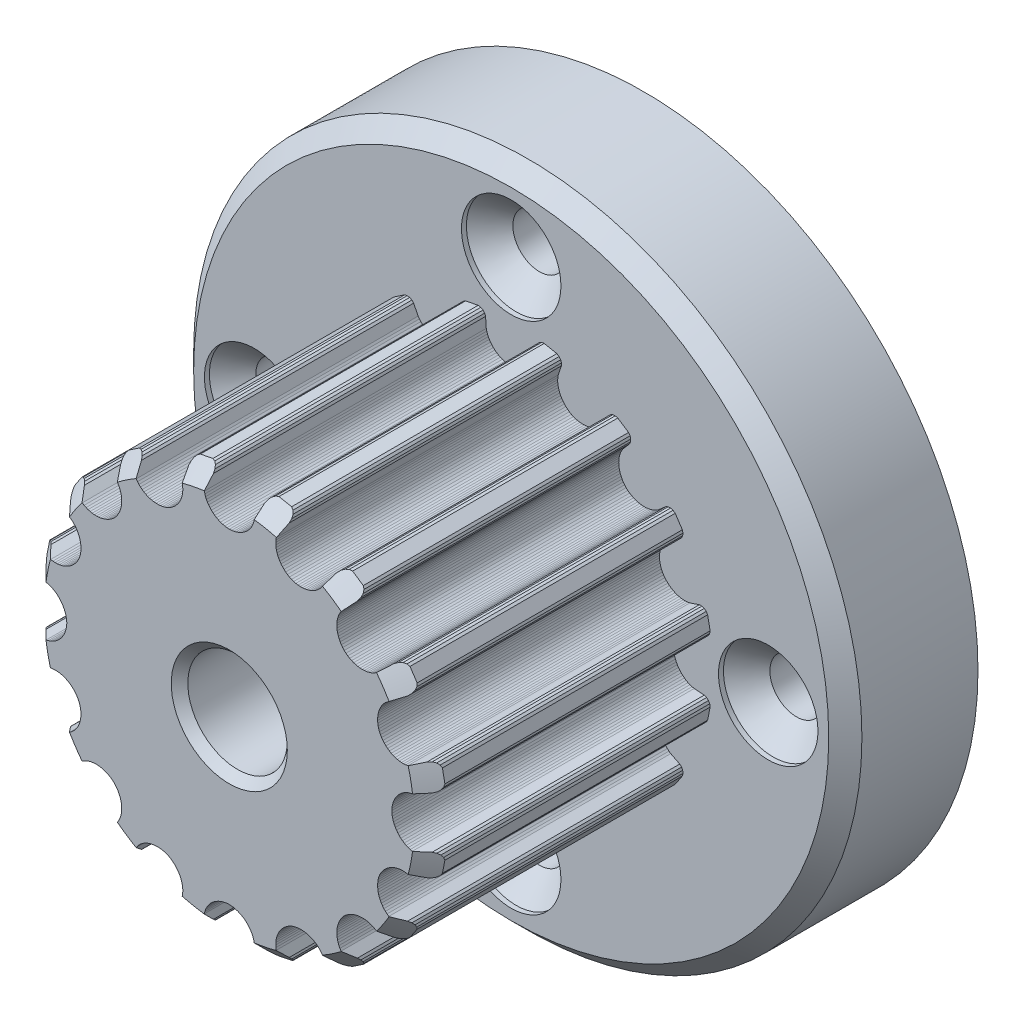
SolidWorks part; units mm, degrees
ref_plane "Front Plane" through (0, 0, 0) normal (0, 0, 1) x (1, 0, 0)
ref_plane "Top Plane" through (0, 0, 0) normal (0, 1, 0) x (1, 0, 0)
ref_plane "Right Plane" through (0, 0, 0) normal (1, 0, 0) x (0, 0, -1)
sketch "Sketch1" plane through (0, 0, 0) normal (0, 0, 1) x (1, 0, 0)
  circle A0 centre (0, 0) radius 15.5
  circle A1 centre (0, 15.5) radius 1.6
  circle A2 centre (15.5, 0) radius 1.6
  circle A3 centre (0, -15.5) radius 1.6
  circle A4 centre (-15.5, 0) radius 1.6
  circle A5 centre (0, 0) radius 20.15
  dimension "D1" = 31
  dimension "D2" = 3.2
  dimension "D3" = 40.3
extrude "Boss-Extrude1" add sketch "Sketch1" along normal blind 8 contours A5 A4 A0 A1 A2 A3 | A4 A0 A3 A2 A1 region at (0, 0, 0) region at (-19.5801, 0, 0)
sketch "Sketch8" plane through (0, 0, 8) normal (0, 0, 1) x (1, 0, 0)
  line L0 (-1.9904, -11.9969) -> (-1.8333, -11.9702)
  line L1 (-1.8333, -11.9702) -> (-1.6992, -11.8961)
  line L2 (-1.6992, -11.8961) -> (-1.5993, -11.7835)
  line L3 (-1.5993, -11.7835) -> (-1.5446, -11.6413)
  line L4 (-1.5446, -11.6413) -> (-1.5027, -11.0359)
  line L5 (-1.5027, -11.0359) -> (-1.4725, -10.9073)
  line L6 (-1.4725, -10.9073) -> (-1.4313, -10.7834)
  line L7 (-1.4313, -10.7834) -> (-1.3796, -10.6646)
  line L8 (-1.3796, -10.6646) -> (-1.3179, -10.5514)
  line L9 (-1.3179, -10.5514) -> (-1.2467, -10.4444)
  line L10 (-1.2467, -10.4444) -> (-1.1667, -10.3438)
  line L11 (-1.1667, -10.3438) -> (-1.0783, -10.2503)
  line L12 (-1.0783, -10.2503) -> (-0.9822, -10.1642)
  line L13 (-0.9822, -10.1642) -> (-0.8789, -10.086)
  line L14 (-0.8789, -10.086) -> (-0.7689, -10.0162)
  line L15 (-0.7689, -10.0162) -> (-0.6528, -9.9552)
  line L16 (-0.6528, -9.9552) -> (-0.5312, -9.9034)
  line L17 (-0.5312, -9.9034) -> (-0.4045, -9.8614)
  line L18 (-0.4045, -9.8614) -> (-0.2734, -9.8296)
  line L19 (-0.2734, -9.8296) -> (-0.1385, -9.8084)
  line L20 (-0.1385, -9.8084) -> (-0.0002, -9.7984)
  line L21 (-0.0002, -9.7984) -> (0.1382, -9.8084)
  line L22 (0.1382, -9.8084) -> (0.2733, -9.8295)
  line L23 (0.2733, -9.8295) -> (0.4045, -9.8613)
  line L24 (0.4045, -9.8613) -> (0.5312, -9.9032)
  line L25 (0.5312, -9.9032) -> (0.6529, -9.9549)
  line L26 (0.6529, -9.9549) -> (0.7691, -10.0159)
  line L27 (0.7691, -10.0159) -> (0.8791, -10.0858)
  line L28 (0.8791, -10.0858) -> (0.9825, -10.1639)
  line L29 (0.9825, -10.1639) -> (1.0786, -10.25)
  line L30 (1.0786, -10.25) -> (1.1669, -10.3436)
  line L31 (1.1669, -10.3436) -> (1.247, -10.4442)
  line L32 (1.247, -10.4442) -> (1.3181, -10.5512)
  line L33 (1.3181, -10.5512) -> (1.3798, -10.6644)
  line L34 (1.3798, -10.6644) -> (1.4315, -10.7832)
  line L35 (1.4315, -10.7832) -> (1.4726, -10.9072)
  line L36 (1.4726, -10.9072) -> (1.5027, -11.0359)
  line L37 (1.5027, -11.0359) -> (1.5446, -11.6413)
  line L38 (1.5446, -11.6413) -> (1.5993, -11.7835)
  line L39 (1.5993, -11.7835) -> (1.6992, -11.8961)
  line L40 (1.6992, -11.8961) -> (1.8333, -11.9702)
  line L41 (1.8333, -11.9702) -> (1.9904, -11.9969)
  line L42 (1.9904, -11.9969) -> (2.7522, -11.8454)
  line L43 (2.7522, -11.8454) -> (2.8871, -11.7606)
  line L44 (2.8871, -11.7606) -> (2.9825, -11.6408)
  line L45 (2.9825, -11.6408) -> (3.0317, -11.4985)
  line L46 (3.0317, -11.4985) -> (3.0279, -11.3462)
  line L47 (3.0279, -11.3462) -> (2.835, -10.7709)
  line L48 (2.835, -10.7709) -> (2.8136, -10.6405)
  line L49 (2.8136, -10.6405) -> (2.8042, -10.5103)
  line L50 (2.8042, -10.5103) -> (2.8066, -10.3807)
  line L51 (2.8066, -10.3807) -> (2.8203, -10.2526)
  line L52 (2.8203, -10.2526) -> (2.8451, -10.1264)
  line L53 (2.8451, -10.1264) -> (2.8805, -10.0029)
  line L54 (2.8805, -10.0029) -> (2.9264, -9.8827)
  line L55 (2.9264, -9.8827) -> (2.9822, -9.7664)
  line L56 (2.9822, -9.7664) -> (3.0478, -9.6546)
  line L57 (3.0478, -9.6546) -> (3.1227, -9.548)
  line L58 (3.1227, -9.548) -> (3.2066, -9.4472)
  line L59 (3.2066, -9.4472) -> (3.2992, -9.3528)
  line L60 (3.2992, -9.3528) -> (3.4001, -9.2656)
  line L61 (3.4001, -9.2656) -> (3.509, -9.186)
  line L62 (3.509, -9.186) -> (3.6256, -9.1148)
  line L63 (3.6256, -9.1148) -> (3.7495, -9.0526)
  line L64 (3.7495, -9.0526) -> (3.8812, -9.0089)
  line L65 (3.8812, -9.0089) -> (4.0141, -8.9767)
  line L66 (4.0141, -8.9767) -> (4.1474, -8.9558)
  line L67 (4.1474, -8.9558) -> (4.2806, -8.9461)
  line L68 (4.2806, -8.9461) -> (4.4128, -8.9473)
  line L69 (4.4128, -8.9473) -> (4.5435, -8.9592)
  line L70 (4.5435, -8.9592) -> (4.6718, -8.9816)
  line L71 (4.6718, -8.9816) -> (4.7972, -9.0143)
  line L72 (4.7972, -9.0143) -> (4.919, -9.057)
  line L73 (4.919, -9.057) -> (5.0364, -9.1097)
  line L74 (5.0364, -9.1097) -> (5.1488, -9.1719)
  line L75 (5.1488, -9.1719) -> (5.2555, -9.2437)
  line L76 (5.2555, -9.2437) -> (5.3558, -9.3246)
  line L77 (5.3558, -9.3246) -> (5.4491, -9.4146)
  line L78 (5.4491, -9.4146) -> (5.5345, -9.5134)
  line L79 (5.5345, -9.5134) -> (5.6115, -9.6208)
  line L80 (5.6115, -9.6208) -> (5.882, -10.164)
  line L81 (5.882, -10.164) -> (5.9869, -10.2745)
  line L82 (5.9869, -10.2745) -> (6.1223, -10.3403)
  line L83 (6.1223, -10.3403) -> (6.2745, -10.3575)
  line L84 (6.2745, -10.3575) -> (6.4299, -10.322)
  line L85 (6.4299, -10.322) -> (7.0757, -9.8905)
  line L86 (7.0757, -9.8905) -> (7.1679, -9.7605)
  line L87 (7.1679, -9.7605) -> (7.2103, -9.6133)
  line L88 (7.2103, -9.6133) -> (7.2013, -9.4631)
  line L89 (7.2013, -9.4631) -> (7.1394, -9.3238)
  line L90 (7.1394, -9.3238) -> (6.741, -8.8661)
  line L91 (6.741, -8.8661) -> (6.6714, -8.7539)
  line L92 (6.6714, -8.7539) -> (6.6129, -8.6371)
  line L93 (6.6129, -8.6371) -> (6.5655, -8.5165)
  line L94 (6.5655, -8.5165) -> (6.5291, -8.3929)
  line L95 (6.5291, -8.3929) -> (6.5037, -8.2669)
  line L96 (6.5037, -8.2669) -> (6.4892, -8.1392)
  line L97 (6.4892, -8.1392) -> (6.4856, -8.0106)
  line L98 (6.4856, -8.0106) -> (6.4926, -7.8817)
  line L99 (6.4926, -7.8817) -> (6.5104, -7.7534)
  line L100 (6.5104, -7.7534) -> (6.5388, -7.6262)
  line L101 (6.5388, -7.6262) -> (6.5778, -7.501)
  line L102 (6.5778, -7.501) -> (6.6272, -7.3784)
  line L103 (6.6272, -7.3784) -> (6.687, -7.2591)
  line L104 (6.687, -7.2591) -> (6.7572, -7.1439)
  line L105 (6.7572, -7.1439) -> (6.8377, -7.0335)
  line L106 (6.8377, -7.0335) -> (6.9284, -6.9286)
  line L107 (6.9284, -6.9286) -> (7.0333, -6.8378)
  line L108 (7.0333, -6.8378) -> (7.1438, -6.7572)
  line L109 (7.1438, -6.7572) -> (7.259, -6.6869)
  line L110 (7.259, -6.6869) -> (7.3783, -6.627)
  line L111 (7.3783, -6.627) -> (7.5009, -6.5775)
  line L112 (7.5009, -6.5775) -> (7.6262, -6.5385)
  line L113 (7.6262, -6.5385) -> (7.7533, -6.5101)
  line L114 (7.7533, -6.5101) -> (7.8817, -6.4923)
  line L115 (7.8817, -6.4923) -> (8.0105, -6.4852)
  line L116 (8.0105, -6.4852) -> (8.1392, -6.4889)
  line L117 (8.1392, -6.4889) -> (8.2669, -6.5034)
  line L118 (8.2669, -6.5034) -> (8.3929, -6.5288)
  line L119 (8.3929, -6.5288) -> (8.5165, -6.5652)
  line L120 (8.5165, -6.5652) -> (8.6371, -6.6127)
  line L121 (8.6371, -6.6127) -> (8.7539, -6.6713)
  line L122 (8.7539, -6.6713) -> (8.8661, -6.741)
  line L123 (8.8661, -6.741) -> (9.3238, -7.1394)
  line L124 (9.3238, -7.1394) -> (9.4631, -7.2013)
  line L125 (9.4631, -7.2013) -> (9.6133, -7.2103)
  line L126 (9.6133, -7.2103) -> (9.7605, -7.1679)
  line L127 (9.7605, -7.1679) -> (9.8905, -7.0757)
  line L128 (9.8905, -7.0757) -> (10.322, -6.4299)
  line L129 (10.322, -6.4299) -> (10.3575, -6.2745)
  line L130 (10.3575, -6.2745) -> (10.3403, -6.1223)
  line L131 (10.3403, -6.1223) -> (10.2745, -5.9869)
  line L132 (10.2745, -5.9869) -> (10.164, -5.882)
  line L133 (10.164, -5.882) -> (9.6208, -5.6115)
  line L134 (9.6208, -5.6115) -> (9.5135, -5.5345)
  line L135 (9.5135, -5.5345) -> (9.4148, -5.449)
  line L136 (9.4148, -5.449) -> (9.3248, -5.3558)
  line L137 (9.3248, -5.3558) -> (9.2439, -5.2554)
  line L138 (9.2439, -5.2554) -> (9.1722, -5.1487)
  line L139 (9.1722, -5.1487) -> (9.11, -5.0363)
  line L140 (9.11, -5.0363) -> (9.0574, -4.9189)
  line L141 (9.0574, -4.9189) -> (9.0146, -4.7971)
  line L142 (9.0146, -4.7971) -> (8.9819, -4.6717)
  line L143 (8.9819, -4.6717) -> (8.9595, -4.5434)
  line L144 (8.9595, -4.5434) -> (8.9476, -4.4128)
  line L145 (8.9476, -4.4128) -> (8.9463, -4.2806)
  line L146 (8.9463, -4.2806) -> (8.956, -4.1475)
  line L147 (8.956, -4.1475) -> (8.9767, -4.0143)
  line L148 (8.9767, -4.0143) -> (9.0088, -3.8815)
  line L149 (9.0088, -3.8815) -> (9.0524, -3.7498)
  line L150 (9.0524, -3.7498) -> (9.1147, -3.6258)
  line L151 (9.1147, -3.6258) -> (9.1859, -3.5091)
  line L152 (9.1859, -3.5091) -> (9.2654, -3.4)
  line L153 (9.2654, -3.4) -> (9.3527, -3.299)
  line L154 (9.3527, -3.299) -> (9.447, -3.2064)
  line L155 (9.447, -3.2064) -> (9.5478, -3.1224)
  line L156 (9.5478, -3.1224) -> (9.6544, -3.0475)
  line L157 (9.6544, -3.0475) -> (9.7662, -2.9819)
  line L158 (9.7662, -2.9819) -> (9.8826, -2.926)
  line L159 (9.8826, -2.926) -> (10.0028, -2.8802)
  line L160 (10.0028, -2.8802) -> (10.1263, -2.8448)
  line L161 (10.1263, -2.8448) -> (10.2525, -2.82)
  line L162 (10.2525, -2.82) -> (10.3807, -2.8064)
  line L163 (10.3807, -2.8064) -> (10.5102, -2.8041)
  line L164 (10.5102, -2.8041) -> (10.6405, -2.8135)
  line L165 (10.6405, -2.8135) -> (10.7709, -2.835)
  line L166 (10.7709, -2.835) -> (11.3462, -3.0279)
  line L167 (11.3462, -3.0279) -> (11.4985, -3.0317)
  line L168 (11.4985, -3.0317) -> (11.6408, -2.9825)
  line L169 (11.6408, -2.9825) -> (11.7606, -2.8871)
  line L170 (11.7606, -2.8871) -> (11.8454, -2.7522)
  line L171 (11.8454, -2.7522) -> (11.9969, -1.9904)
  line L172 (11.9969, -1.9904) -> (11.9702, -1.8333)
  line L173 (11.9702, -1.8333) -> (11.8961, -1.6992)
  line L174 (11.8961, -1.6992) -> (11.7835, -1.5993)
  line L175 (11.7835, -1.5993) -> (11.6413, -1.5446)
  line L176 (11.6413, -1.5446) -> (11.0359, -1.5027)
  line L177 (11.0359, -1.5027) -> (10.9073, -1.4725)
  line L178 (10.9073, -1.4725) -> (10.7834, -1.4313)
  line L179 (10.7834, -1.4313) -> (10.6646, -1.3796)
  line L180 (10.6646, -1.3796) -> (10.5514, -1.3179)
  line L181 (10.5514, -1.3179) -> (10.4444, -1.2467)
  line L182 (10.4444, -1.2467) -> (10.3438, -1.1667)
  line L183 (10.3438, -1.1667) -> (10.2503, -1.0783)
  line L184 (10.2503, -1.0783) -> (10.1642, -0.9822)
  line L185 (10.1642, -0.9822) -> (10.086, -0.8789)
  line L186 (10.086, -0.8789) -> (10.0162, -0.7689)
  line L187 (10.0162, -0.7689) -> (9.9552, -0.6528)
  line L188 (9.9552, -0.6528) -> (9.9034, -0.5312)
  line L189 (9.9034, -0.5312) -> (9.8614, -0.4045)
  line L190 (9.8614, -0.4045) -> (9.8296, -0.2734)
  line L191 (9.8296, -0.2734) -> (9.8084, -0.1385)
  line L192 (9.8084, -0.1385) -> (9.7984, -0.0002)
  line L193 (9.7984, -0.0002) -> (9.8084, 0.1382)
  line L194 (9.8084, 0.1382) -> (9.8295, 0.2733)
  line L195 (9.8295, 0.2733) -> (9.8613, 0.4045)
  line L196 (9.8613, 0.4045) -> (9.9032, 0.5312)
  line L197 (9.9032, 0.5312) -> (9.9549, 0.6529)
  line L198 (9.9549, 0.6529) -> (10.0159, 0.7691)
  line L199 (10.0159, 0.7691) -> (10.0858, 0.8791)
  line L200 (10.0858, 0.8791) -> (10.1639, 0.9825)
  line L201 (10.1639, 0.9825) -> (10.25, 1.0786)
  line L202 (10.25, 1.0786) -> (10.3436, 1.1669)
  line L203 (10.3436, 1.1669) -> (10.4442, 1.247)
  line L204 (10.4442, 1.247) -> (10.5512, 1.3181)
  line L205 (10.5512, 1.3181) -> (10.6644, 1.3798)
  line L206 (10.6644, 1.3798) -> (10.7832, 1.4315)
  line L207 (10.7832, 1.4315) -> (10.9072, 1.4726)
  line L208 (10.9072, 1.4726) -> (11.0359, 1.5027)
  line L209 (11.0359, 1.5027) -> (11.6413, 1.5446)
  line L210 (11.6413, 1.5446) -> (11.7835, 1.5993)
  line L211 (11.7835, 1.5993) -> (11.8961, 1.6992)
  line L212 (11.8961, 1.6992) -> (11.9702, 1.8333)
  line L213 (11.9702, 1.8333) -> (11.9969, 1.9904)
  line L214 (11.9969, 1.9904) -> (11.8454, 2.7522)
  line L215 (11.8454, 2.7522) -> (11.7606, 2.8871)
  line L216 (11.7606, 2.8871) -> (11.6408, 2.9825)
  line L217 (11.6408, 2.9825) -> (11.4985, 3.0317)
  line L218 (11.4985, 3.0317) -> (11.3462, 3.0279)
  line L219 (11.3462, 3.0279) -> (10.7709, 2.835)
  line L220 (10.7709, 2.835) -> (10.6405, 2.8136)
  line L221 (10.6405, 2.8136) -> (10.5103, 2.8042)
  line L222 (10.5103, 2.8042) -> (10.3807, 2.8066)
  line L223 (10.3807, 2.8066) -> (10.2526, 2.8203)
  line L224 (10.2526, 2.8203) -> (10.1264, 2.8451)
  line L225 (10.1264, 2.8451) -> (10.0029, 2.8805)
  line L226 (10.0029, 2.8805) -> (9.8827, 2.9264)
  line L227 (9.8827, 2.9264) -> (9.7664, 2.9822)
  line L228 (9.7664, 2.9822) -> (9.6546, 3.0478)
  line L229 (9.6546, 3.0478) -> (9.548, 3.1227)
  line L230 (9.548, 3.1227) -> (9.4472, 3.2066)
  line L231 (9.4472, 3.2066) -> (9.3528, 3.2992)
  line L232 (9.3528, 3.2992) -> (9.2656, 3.4001)
  line L233 (9.2656, 3.4001) -> (9.186, 3.509)
  line L234 (9.186, 3.509) -> (9.1148, 3.6256)
  line L235 (9.1148, 3.6256) -> (9.0526, 3.7495)
  line L236 (9.0526, 3.7495) -> (9.0089, 3.8812)
  line L237 (9.0089, 3.8812) -> (8.9767, 4.0141)
  line L238 (8.9767, 4.0141) -> (8.9558, 4.1474)
  line L239 (8.9558, 4.1474) -> (8.9461, 4.2806)
  line L240 (8.9461, 4.2806) -> (8.9473, 4.4128)
  line L241 (8.9473, 4.4128) -> (8.9592, 4.5435)
  line L242 (8.9592, 4.5435) -> (8.9816, 4.6718)
  line L243 (8.9816, 4.6718) -> (9.0143, 4.7972)
  line L244 (9.0143, 4.7972) -> (9.057, 4.919)
  line L245 (9.057, 4.919) -> (9.1097, 5.0364)
  line L246 (9.1097, 5.0364) -> (9.1719, 5.1488)
  line L247 (9.1719, 5.1488) -> (9.2437, 5.2555)
  line L248 (9.2437, 5.2555) -> (9.3246, 5.3558)
  line L249 (9.3246, 5.3558) -> (9.4146, 5.4491)
  line L250 (9.4146, 5.4491) -> (9.5134, 5.5345)
  line L251 (9.5134, 5.5345) -> (9.6208, 5.6115)
  line L252 (9.6208, 5.6115) -> (10.164, 5.882)
  line L253 (10.164, 5.882) -> (10.2745, 5.9869)
  line L254 (10.2745, 5.9869) -> (10.3403, 6.1223)
  line L255 (10.3403, 6.1223) -> (10.3575, 6.2745)
  line L256 (10.3575, 6.2745) -> (10.322, 6.4299)
  line L257 (10.322, 6.4299) -> (9.8905, 7.0757)
  line L258 (9.8905, 7.0757) -> (9.7605, 7.1679)
  line L259 (9.7605, 7.1679) -> (9.6133, 7.2103)
  line L260 (9.6133, 7.2103) -> (9.4631, 7.2013)
  line L261 (9.4631, 7.2013) -> (9.3238, 7.1394)
  line L262 (9.3238, 7.1394) -> (8.8661, 6.741)
  line L263 (8.8661, 6.741) -> (8.7539, 6.6714)
  line L264 (8.7539, 6.6714) -> (8.6371, 6.6129)
  line L265 (8.6371, 6.6129) -> (8.5165, 6.5655)
  line L266 (8.5165, 6.5655) -> (8.3929, 6.5291)
  line L267 (8.3929, 6.5291) -> (8.2669, 6.5037)
  line L268 (8.2669, 6.5037) -> (8.1392, 6.4892)
  line L269 (8.1392, 6.4892) -> (8.0106, 6.4856)
  line L270 (8.0106, 6.4856) -> (7.8817, 6.4926)
  line L271 (7.8817, 6.4926) -> (7.7534, 6.5104)
  line L272 (7.7534, 6.5104) -> (7.6262, 6.5388)
  line L273 (7.6262, 6.5388) -> (7.501, 6.5778)
  line L274 (7.501, 6.5778) -> (7.3784, 6.6272)
  line L275 (7.3784, 6.6272) -> (7.2591, 6.687)
  line L276 (7.2591, 6.687) -> (7.1439, 6.7572)
  line L277 (7.1439, 6.7572) -> (7.0335, 6.8377)
  line L278 (7.0335, 6.8377) -> (6.9286, 6.9284)
  line L279 (6.9286, 6.9284) -> (6.8378, 7.0333)
  line L280 (6.8378, 7.0333) -> (6.7572, 7.1438)
  line L281 (6.7572, 7.1438) -> (6.6869, 7.259)
  line L282 (6.6869, 7.259) -> (6.627, 7.3783)
  line L283 (6.627, 7.3783) -> (6.5775, 7.5009)
  line L284 (6.5775, 7.5009) -> (6.5385, 7.6262)
  line L285 (6.5385, 7.6262) -> (6.5101, 7.7533)
  line L286 (6.5101, 7.7533) -> (6.4923, 7.8817)
  line L287 (6.4923, 7.8817) -> (6.4852, 8.0105)
  line L288 (6.4852, 8.0105) -> (6.4889, 8.1392)
  line L289 (6.4889, 8.1392) -> (6.5034, 8.2669)
  line L290 (6.5034, 8.2669) -> (6.5288, 8.3929)
  line L291 (6.5288, 8.3929) -> (6.5652, 8.5165)
  line L292 (6.5652, 8.5165) -> (6.6127, 8.6371)
  line L293 (6.6127, 8.6371) -> (6.6713, 8.7539)
  line L294 (6.6713, 8.7539) -> (6.741, 8.8661)
  line L295 (6.741, 8.8661) -> (7.1394, 9.3238)
  line L296 (7.1394, 9.3238) -> (7.2013, 9.4631)
  line L297 (7.2013, 9.4631) -> (7.2103, 9.6133)
  line L298 (7.2103, 9.6133) -> (7.1679, 9.7605)
  line L299 (7.1679, 9.7605) -> (7.0757, 9.8905)
  line L300 (7.0757, 9.8905) -> (6.4299, 10.322)
  line L301 (6.4299, 10.322) -> (6.2745, 10.3575)
  line L302 (6.2745, 10.3575) -> (6.1223, 10.3403)
  line L303 (6.1223, 10.3403) -> (5.9869, 10.2745)
  line L304 (5.9869, 10.2745) -> (5.882, 10.164)
  line L305 (5.882, 10.164) -> (5.6115, 9.6208)
  line L306 (5.6115, 9.6208) -> (5.5345, 9.5135)
  line L307 (5.5345, 9.5135) -> (5.449, 9.4148)
  line L308 (5.449, 9.4148) -> (5.3558, 9.3248)
  line L309 (5.3558, 9.3248) -> (5.2554, 9.2439)
  line L310 (5.2554, 9.2439) -> (5.1487, 9.1722)
  line L311 (5.1487, 9.1722) -> (5.0363, 9.11)
  line L312 (5.0363, 9.11) -> (4.9189, 9.0574)
  line L313 (4.9189, 9.0574) -> (4.7971, 9.0146)
  line L314 (4.7971, 9.0146) -> (4.6717, 8.9819)
  line L315 (4.6717, 8.9819) -> (4.5434, 8.9595)
  line L316 (4.5434, 8.9595) -> (4.4128, 8.9476)
  line L317 (4.4128, 8.9476) -> (4.2806, 8.9463)
  line L318 (4.2806, 8.9463) -> (4.1475, 8.956)
  line L319 (4.1475, 8.956) -> (4.0143, 8.9767)
  line L320 (4.0143, 8.9767) -> (3.8815, 9.0088)
  line L321 (3.8815, 9.0088) -> (3.7498, 9.0524)
  line L322 (3.7498, 9.0524) -> (3.6258, 9.1147)
  line L323 (3.6258, 9.1147) -> (3.5091, 9.1859)
  line L324 (3.5091, 9.1859) -> (3.4, 9.2654)
  line L325 (3.4, 9.2654) -> (3.299, 9.3527)
  line L326 (3.299, 9.3527) -> (3.2064, 9.447)
  line L327 (3.2064, 9.447) -> (3.1224, 9.5478)
  line L328 (3.1224, 9.5478) -> (3.0475, 9.6544)
  line L329 (3.0475, 9.6544) -> (2.9819, 9.7662)
  line L330 (2.9819, 9.7662) -> (2.926, 9.8826)
  line L331 (2.926, 9.8826) -> (2.8802, 10.0028)
  line L332 (2.8802, 10.0028) -> (2.8448, 10.1263)
  line L333 (2.8448, 10.1263) -> (2.82, 10.2525)
  line L334 (2.82, 10.2525) -> (2.8064, 10.3807)
  line L335 (2.8064, 10.3807) -> (2.8041, 10.5102)
  line L336 (2.8041, 10.5102) -> (2.8135, 10.6405)
  line L337 (2.8135, 10.6405) -> (2.835, 10.7709)
  line L338 (2.835, 10.7709) -> (3.0279, 11.3462)
  line L339 (3.0279, 11.3462) -> (3.0317, 11.4985)
  line L340 (3.0317, 11.4985) -> (2.9825, 11.6408)
  line L341 (2.9825, 11.6408) -> (2.8871, 11.7606)
  line L342 (2.8871, 11.7606) -> (2.7522, 11.8454)
  line L343 (2.7522, 11.8454) -> (1.9904, 11.9969)
  line L344 (1.9904, 11.9969) -> (1.8333, 11.9702)
  line L345 (1.8333, 11.9702) -> (1.6992, 11.8961)
  line L346 (1.6992, 11.8961) -> (1.5993, 11.7835)
  line L347 (1.5993, 11.7835) -> (1.5446, 11.6413)
  line L348 (1.5446, 11.6413) -> (1.5027, 11.0359)
  line L349 (1.5027, 11.0359) -> (1.4725, 10.9073)
  line L350 (1.4725, 10.9073) -> (1.4313, 10.7834)
  line L351 (1.4313, 10.7834) -> (1.3796, 10.6646)
  line L352 (1.3796, 10.6646) -> (1.3179, 10.5514)
  line L353 (1.3179, 10.5514) -> (1.2467, 10.4444)
  line L354 (1.2467, 10.4444) -> (1.1667, 10.3438)
  line L355 (1.1667, 10.3438) -> (1.0783, 10.2503)
  line L356 (1.0783, 10.2503) -> (0.9822, 10.1642)
  line L357 (0.9822, 10.1642) -> (0.8789, 10.086)
  line L358 (0.8789, 10.086) -> (0.7689, 10.0162)
  line L359 (0.7689, 10.0162) -> (0.6528, 9.9552)
  line L360 (0.6528, 9.9552) -> (0.5312, 9.9034)
  line L361 (0.5312, 9.9034) -> (0.4045, 9.8614)
  line L362 (0.4045, 9.8614) -> (0.2734, 9.8296)
  line L363 (0.2734, 9.8296) -> (0.1385, 9.8084)
  line L364 (0.1385, 9.8084) -> (0.0002, 9.7984)
  line L365 (0.0002, 9.7984) -> (-0.1382, 9.8084)
  line L366 (-0.1382, 9.8084) -> (-0.2733, 9.8295)
  line L367 (-0.2733, 9.8295) -> (-0.4045, 9.8613)
  line L368 (-0.4045, 9.8613) -> (-0.5312, 9.9032)
  line L369 (-0.5312, 9.9032) -> (-0.6529, 9.9549)
  line L370 (-0.6529, 9.9549) -> (-0.7691, 10.0159)
  line L371 (-0.7691, 10.0159) -> (-0.8791, 10.0858)
  line L372 (-0.8791, 10.0858) -> (-0.9825, 10.1639)
  line L373 (-0.9825, 10.1639) -> (-1.0786, 10.25)
  line L374 (-1.0786, 10.25) -> (-1.1669, 10.3436)
  line L375 (-1.1669, 10.3436) -> (-1.247, 10.4442)
  line L376 (-1.247, 10.4442) -> (-1.3181, 10.5512)
  line L377 (-1.3181, 10.5512) -> (-1.3798, 10.6644)
  line L378 (-1.3798, 10.6644) -> (-1.4315, 10.7832)
  line L379 (-1.4315, 10.7832) -> (-1.4726, 10.9072)
  line L380 (-1.4726, 10.9072) -> (-1.5027, 11.0359)
  line L381 (-1.5027, 11.0359) -> (-1.5446, 11.6413)
  line L382 (-1.5446, 11.6413) -> (-1.5993, 11.7835)
  line L383 (-1.5993, 11.7835) -> (-1.6992, 11.8961)
  line L384 (-1.6992, 11.8961) -> (-1.8333, 11.9702)
  line L385 (-1.8333, 11.9702) -> (-1.9904, 11.9969)
  line L386 (-1.9904, 11.9969) -> (-2.7522, 11.8454)
  line L387 (-2.7522, 11.8454) -> (-2.8871, 11.7606)
  line L388 (-2.8871, 11.7606) -> (-2.9825, 11.6408)
  line L389 (-2.9825, 11.6408) -> (-3.0317, 11.4985)
  line L390 (-3.0317, 11.4985) -> (-3.0279, 11.3462)
  line L391 (-3.0279, 11.3462) -> (-2.835, 10.7709)
  line L392 (-2.835, 10.7709) -> (-2.8136, 10.6405)
  line L393 (-2.8136, 10.6405) -> (-2.8042, 10.5103)
  line L394 (-2.8042, 10.5103) -> (-2.8066, 10.3807)
  line L395 (-2.8066, 10.3807) -> (-2.8203, 10.2526)
  line L396 (-2.8203, 10.2526) -> (-2.8451, 10.1264)
  line L397 (-2.8451, 10.1264) -> (-2.8805, 10.0029)
  line L398 (-2.8805, 10.0029) -> (-2.9264, 9.8827)
  line L399 (-2.9264, 9.8827) -> (-2.9822, 9.7664)
  line L400 (-2.9822, 9.7664) -> (-3.0478, 9.6546)
  line L401 (-3.0478, 9.6546) -> (-3.1227, 9.548)
  line L402 (-3.1227, 9.548) -> (-3.2066, 9.4472)
  line L403 (-3.2066, 9.4472) -> (-3.2992, 9.3528)
  line L404 (-3.2992, 9.3528) -> (-3.4001, 9.2656)
  line L405 (-3.4001, 9.2656) -> (-3.509, 9.186)
  line L406 (-3.509, 9.186) -> (-3.6256, 9.1148)
  line L407 (-3.6256, 9.1148) -> (-3.7495, 9.0526)
  line L408 (-3.7495, 9.0526) -> (-3.8812, 9.0089)
  line L409 (-3.8812, 9.0089) -> (-4.0141, 8.9767)
  line L410 (-4.0141, 8.9767) -> (-4.1474, 8.9558)
  line L411 (-4.1474, 8.9558) -> (-4.2806, 8.9461)
  line L412 (-4.2806, 8.9461) -> (-4.4128, 8.9473)
  line L413 (-4.4128, 8.9473) -> (-4.5435, 8.9592)
  line L414 (-4.5435, 8.9592) -> (-4.6718, 8.9816)
  line L415 (-4.6718, 8.9816) -> (-4.7972, 9.0143)
  line L416 (-4.7972, 9.0143) -> (-4.919, 9.057)
  line L417 (-4.919, 9.057) -> (-5.0364, 9.1097)
  line L418 (-5.0364, 9.1097) -> (-5.1488, 9.1719)
  line L419 (-5.1488, 9.1719) -> (-5.2555, 9.2437)
  line L420 (-5.2555, 9.2437) -> (-5.3558, 9.3246)
  line L421 (-5.3558, 9.3246) -> (-5.4491, 9.4146)
  line L422 (-5.4491, 9.4146) -> (-5.5345, 9.5134)
  line L423 (-5.5345, 9.5134) -> (-5.6115, 9.6208)
  line L424 (-5.6115, 9.6208) -> (-5.882, 10.164)
  line L425 (-5.882, 10.164) -> (-5.9869, 10.2745)
  line L426 (-5.9869, 10.2745) -> (-6.1223, 10.3403)
  line L427 (-6.1223, 10.3403) -> (-6.2745, 10.3575)
  line L428 (-6.2745, 10.3575) -> (-6.4299, 10.322)
  line L429 (-6.4299, 10.322) -> (-7.0757, 9.8905)
  line L430 (-7.0757, 9.8905) -> (-7.1679, 9.7605)
  line L431 (-7.1679, 9.7605) -> (-7.2103, 9.6133)
  line L432 (-7.2103, 9.6133) -> (-7.2013, 9.4631)
  line L433 (-7.2013, 9.4631) -> (-7.1394, 9.3238)
  line L434 (-7.1394, 9.3238) -> (-6.741, 8.8661)
  line L435 (-6.741, 8.8661) -> (-6.6714, 8.7539)
  line L436 (-6.6714, 8.7539) -> (-6.6129, 8.6371)
  line L437 (-6.6129, 8.6371) -> (-6.5655, 8.5165)
  line L438 (-6.5655, 8.5165) -> (-6.5291, 8.3929)
  line L439 (-6.5291, 8.3929) -> (-6.5037, 8.2669)
  line L440 (-6.5037, 8.2669) -> (-6.4892, 8.1392)
  line L441 (-6.4892, 8.1392) -> (-6.4856, 8.0106)
  line L442 (-6.4856, 8.0106) -> (-6.4926, 7.8817)
  line L443 (-6.4926, 7.8817) -> (-6.5104, 7.7534)
  line L444 (-6.5104, 7.7534) -> (-6.5388, 7.6262)
  line L445 (-6.5388, 7.6262) -> (-6.5778, 7.501)
  line L446 (-6.5778, 7.501) -> (-6.6272, 7.3784)
  line L447 (-6.6272, 7.3784) -> (-6.687, 7.2591)
  line L448 (-6.687, 7.2591) -> (-6.7572, 7.1439)
  line L449 (-6.7572, 7.1439) -> (-6.8377, 7.0335)
  line L450 (-6.8377, 7.0335) -> (-6.9284, 6.9286)
  line L451 (-6.9284, 6.9286) -> (-7.0333, 6.8378)
  line L452 (-7.0333, 6.8378) -> (-7.1438, 6.7572)
  line L453 (-7.1438, 6.7572) -> (-7.259, 6.6869)
  line L454 (-7.259, 6.6869) -> (-7.3783, 6.627)
  line L455 (-7.3783, 6.627) -> (-7.5009, 6.5775)
  line L456 (-7.5009, 6.5775) -> (-7.6262, 6.5385)
  line L457 (-7.6262, 6.5385) -> (-7.7533, 6.5101)
  line L458 (-7.7533, 6.5101) -> (-7.8817, 6.4923)
  line L459 (-7.8817, 6.4923) -> (-8.0105, 6.4852)
  line L460 (-8.0105, 6.4852) -> (-8.1392, 6.4889)
  line L461 (-8.1392, 6.4889) -> (-8.2669, 6.5034)
  line L462 (-8.2669, 6.5034) -> (-8.3929, 6.5288)
  line L463 (-8.3929, 6.5288) -> (-8.5165, 6.5652)
  line L464 (-8.5165, 6.5652) -> (-8.6371, 6.6127)
  line L465 (-8.6371, 6.6127) -> (-8.7539, 6.6713)
  line L466 (-8.7539, 6.6713) -> (-8.8661, 6.741)
  line L467 (-8.8661, 6.741) -> (-9.3238, 7.1394)
  line L468 (-9.3238, 7.1394) -> (-9.4631, 7.2013)
  line L469 (-9.4631, 7.2013) -> (-9.6133, 7.2103)
  line L470 (-9.6133, 7.2103) -> (-9.7605, 7.1679)
  line L471 (-9.7605, 7.1679) -> (-9.8905, 7.0757)
  line L472 (-9.8905, 7.0757) -> (-10.322, 6.4299)
  line L473 (-10.322, 6.4299) -> (-10.3575, 6.2745)
  line L474 (-10.3575, 6.2745) -> (-10.3403, 6.1223)
  line L475 (-10.3403, 6.1223) -> (-10.2745, 5.9869)
  line L476 (-10.2745, 5.9869) -> (-10.164, 5.882)
  line L477 (-10.164, 5.882) -> (-9.6208, 5.6115)
  line L478 (-9.6208, 5.6115) -> (-9.5135, 5.5345)
  line L479 (-9.5135, 5.5345) -> (-9.4148, 5.449)
  line L480 (-9.4148, 5.449) -> (-9.3248, 5.3558)
  line L481 (-9.3248, 5.3558) -> (-9.2439, 5.2554)
  line L482 (-9.2439, 5.2554) -> (-9.1722, 5.1487)
  line L483 (-9.1722, 5.1487) -> (-9.11, 5.0363)
  line L484 (-9.11, 5.0363) -> (-9.0574, 4.9189)
  line L485 (-9.0574, 4.9189) -> (-9.0146, 4.7971)
  line L486 (-9.0146, 4.7971) -> (-8.9819, 4.6717)
  line L487 (-8.9819, 4.6717) -> (-8.9595, 4.5434)
  line L488 (-8.9595, 4.5434) -> (-8.9476, 4.4128)
  line L489 (-8.9476, 4.4128) -> (-8.9463, 4.2806)
  line L490 (-8.9463, 4.2806) -> (-8.956, 4.1475)
  line L491 (-8.956, 4.1475) -> (-8.9767, 4.0143)
  line L492 (-8.9767, 4.0143) -> (-9.0088, 3.8815)
  line L493 (-9.0088, 3.8815) -> (-9.0524, 3.7498)
  line L494 (-9.0524, 3.7498) -> (-9.1147, 3.6258)
  line L495 (-9.1147, 3.6258) -> (-9.1859, 3.5091)
  line L496 (-9.1859, 3.5091) -> (-9.2654, 3.4)
  line L497 (-9.2654, 3.4) -> (-9.3527, 3.299)
  line L498 (-9.3527, 3.299) -> (-9.447, 3.2064)
  line L499 (-9.447, 3.2064) -> (-9.5478, 3.1224)
  line L500 (-9.5478, 3.1224) -> (-9.6544, 3.0475)
  line L501 (-9.6544, 3.0475) -> (-9.7662, 2.9819)
  line L502 (-9.7662, 2.9819) -> (-9.8826, 2.926)
  line L503 (-9.8826, 2.926) -> (-10.0028, 2.8802)
  line L504 (-10.0028, 2.8802) -> (-10.1263, 2.8448)
  line L505 (-10.1263, 2.8448) -> (-10.2525, 2.82)
  line L506 (-10.2525, 2.82) -> (-10.3807, 2.8064)
  line L507 (-10.3807, 2.8064) -> (-10.5102, 2.8041)
  line L508 (-10.5102, 2.8041) -> (-10.6405, 2.8135)
  line L509 (-10.6405, 2.8135) -> (-10.7709, 2.835)
  line L510 (-10.7709, 2.835) -> (-11.3462, 3.0279)
  line L511 (-11.3462, 3.0279) -> (-11.4985, 3.0317)
  line L512 (-11.4985, 3.0317) -> (-11.6408, 2.9825)
  line L513 (-11.6408, 2.9825) -> (-11.7606, 2.8871)
  line L514 (-11.7606, 2.8871) -> (-11.8454, 2.7522)
  line L515 (-11.8454, 2.7522) -> (-11.9969, 1.9904)
  line L516 (-11.9969, 1.9904) -> (-11.9702, 1.8333)
  line L517 (-11.9702, 1.8333) -> (-11.8961, 1.6992)
  line L518 (-11.8961, 1.6992) -> (-11.7835, 1.5993)
  line L519 (-11.7835, 1.5993) -> (-11.6413, 1.5446)
  line L520 (-11.6413, 1.5446) -> (-11.0359, 1.5027)
  line L521 (-11.0359, 1.5027) -> (-10.9073, 1.4725)
  line L522 (-10.9073, 1.4725) -> (-10.7834, 1.4313)
  line L523 (-10.7834, 1.4313) -> (-10.6646, 1.3796)
  line L524 (-10.6646, 1.3796) -> (-10.5514, 1.3179)
  line L525 (-10.5514, 1.3179) -> (-10.4444, 1.2467)
  line L526 (-10.4444, 1.2467) -> (-10.3438, 1.1667)
  line L527 (-10.3438, 1.1667) -> (-10.2503, 1.0783)
  line L528 (-10.2503, 1.0783) -> (-10.1642, 0.9822)
  line L529 (-10.1642, 0.9822) -> (-10.086, 0.8789)
  line L530 (-10.086, 0.8789) -> (-10.0162, 0.7689)
  line L531 (-10.0162, 0.7689) -> (-9.9552, 0.6528)
  line L532 (-9.9552, 0.6528) -> (-9.9034, 0.5312)
  line L533 (-9.9034, 0.5312) -> (-9.8614, 0.4045)
  line L534 (-9.8614, 0.4045) -> (-9.8296, 0.2734)
  line L535 (-9.8296, 0.2734) -> (-9.8084, 0.1385)
  line L536 (-9.8084, 0.1385) -> (-9.7984, 0.0002)
  line L537 (-9.7984, 0.0002) -> (-9.8084, -0.1382)
  line L538 (-9.8084, -0.1382) -> (-9.8295, -0.2733)
  line L539 (-9.8295, -0.2733) -> (-9.8613, -0.4045)
  line L540 (-9.8613, -0.4045) -> (-9.9032, -0.5312)
  line L541 (-9.9032, -0.5312) -> (-9.9549, -0.6529)
  line L542 (-9.9549, -0.6529) -> (-10.0159, -0.7691)
  line L543 (-10.0159, -0.7691) -> (-10.0858, -0.8791)
  line L544 (-10.0858, -0.8791) -> (-10.1639, -0.9825)
  line L545 (-10.1639, -0.9825) -> (-10.25, -1.0786)
  line L546 (-10.25, -1.0786) -> (-10.3436, -1.1669)
  line L547 (-10.3436, -1.1669) -> (-10.4442, -1.247)
  line L548 (-10.4442, -1.247) -> (-10.5512, -1.3181)
  line L549 (-10.5512, -1.3181) -> (-10.6644, -1.3798)
  line L550 (-10.6644, -1.3798) -> (-10.7832, -1.4315)
  line L551 (-10.7832, -1.4315) -> (-10.9072, -1.4726)
  line L552 (-10.9072, -1.4726) -> (-11.0359, -1.5027)
  line L553 (-11.0359, -1.5027) -> (-11.6413, -1.5446)
  line L554 (-11.6413, -1.5446) -> (-11.7835, -1.5993)
  line L555 (-11.7835, -1.5993) -> (-11.8961, -1.6992)
  line L556 (-11.8961, -1.6992) -> (-11.9702, -1.8333)
  line L557 (-11.9702, -1.8333) -> (-11.9969, -1.9904)
  line L558 (-11.9969, -1.9904) -> (-11.8454, -2.7522)
  line L559 (-11.8454, -2.7522) -> (-11.7606, -2.8871)
  line L560 (-11.7606, -2.8871) -> (-11.6408, -2.9825)
  line L561 (-11.6408, -2.9825) -> (-11.4985, -3.0317)
  line L562 (-11.4985, -3.0317) -> (-11.3462, -3.0279)
  line L563 (-11.3462, -3.0279) -> (-10.7709, -2.835)
  line L564 (-10.7709, -2.835) -> (-10.6405, -2.8136)
  line L565 (-10.6405, -2.8136) -> (-10.5103, -2.8042)
  line L566 (-10.5103, -2.8042) -> (-10.3807, -2.8066)
  line L567 (-10.3807, -2.8066) -> (-10.2526, -2.8203)
  line L568 (-10.2526, -2.8203) -> (-10.1264, -2.8451)
  line L569 (-10.1264, -2.8451) -> (-10.0029, -2.8805)
  line L570 (-10.0029, -2.8805) -> (-9.8827, -2.9264)
  line L571 (-9.8827, -2.9264) -> (-9.7664, -2.9822)
  line L572 (-9.7664, -2.9822) -> (-9.6546, -3.0478)
  line L573 (-9.6546, -3.0478) -> (-9.548, -3.1227)
  line L574 (-9.548, -3.1227) -> (-9.4472, -3.2066)
  line L575 (-9.4472, -3.2066) -> (-9.3528, -3.2992)
  line L576 (-9.3528, -3.2992) -> (-9.2656, -3.4001)
  line L577 (-9.2656, -3.4001) -> (-9.186, -3.509)
  line L578 (-9.186, -3.509) -> (-9.1148, -3.6256)
  line L579 (-9.1148, -3.6256) -> (-9.0526, -3.7495)
  line L580 (-9.0526, -3.7495) -> (-9.0089, -3.8812)
  line L581 (-9.0089, -3.8812) -> (-8.9767, -4.0141)
  line L582 (-8.9767, -4.0141) -> (-8.9558, -4.1474)
  line L583 (-8.9558, -4.1474) -> (-8.9461, -4.2806)
  line L584 (-8.9461, -4.2806) -> (-8.9473, -4.4128)
  line L585 (-8.9473, -4.4128) -> (-8.9592, -4.5435)
  line L586 (-8.9592, -4.5435) -> (-8.9816, -4.6718)
  line L587 (-8.9816, -4.6718) -> (-9.0143, -4.7972)
  line L588 (-9.0143, -4.7972) -> (-9.057, -4.919)
  line L589 (-9.057, -4.919) -> (-9.1097, -5.0364)
  line L590 (-9.1097, -5.0364) -> (-9.1719, -5.1488)
  line L591 (-9.1719, -5.1488) -> (-9.2437, -5.2555)
  line L592 (-9.2437, -5.2555) -> (-9.3246, -5.3558)
  line L593 (-9.3246, -5.3558) -> (-9.4146, -5.4491)
  line L594 (-9.4146, -5.4491) -> (-9.5134, -5.5345)
  line L595 (-9.5134, -5.5345) -> (-9.6208, -5.6115)
  line L596 (-9.6208, -5.6115) -> (-10.164, -5.882)
  line L597 (-10.164, -5.882) -> (-10.2745, -5.9869)
  line L598 (-10.2745, -5.9869) -> (-10.3403, -6.1223)
  line L599 (-10.3403, -6.1223) -> (-10.3575, -6.2745)
  line L600 (-10.3575, -6.2745) -> (-10.322, -6.4299)
  line L601 (-10.322, -6.4299) -> (-9.8905, -7.0757)
  line L602 (-9.8905, -7.0757) -> (-9.7605, -7.1679)
  line L603 (-9.7605, -7.1679) -> (-9.6133, -7.2103)
  line L604 (-9.6133, -7.2103) -> (-9.4631, -7.2013)
  line L605 (-9.4631, -7.2013) -> (-9.3238, -7.1394)
  line L606 (-9.3238, -7.1394) -> (-8.8661, -6.741)
  line L607 (-8.8661, -6.741) -> (-8.7539, -6.6714)
  line L608 (-8.7539, -6.6714) -> (-8.6371, -6.6129)
  line L609 (-8.6371, -6.6129) -> (-8.5165, -6.5655)
  line L610 (-8.5165, -6.5655) -> (-8.3929, -6.5291)
  line L611 (-8.3929, -6.5291) -> (-8.2669, -6.5037)
  line L612 (-8.2669, -6.5037) -> (-8.1392, -6.4892)
  line L613 (-8.1392, -6.4892) -> (-8.0106, -6.4856)
  line L614 (-8.0106, -6.4856) -> (-7.8817, -6.4926)
  line L615 (-7.8817, -6.4926) -> (-7.7534, -6.5104)
  line L616 (-7.7534, -6.5104) -> (-7.6262, -6.5388)
  line L617 (-7.6262, -6.5388) -> (-7.501, -6.5778)
  line L618 (-7.501, -6.5778) -> (-7.3784, -6.6272)
  line L619 (-7.3784, -6.6272) -> (-7.2591, -6.687)
  line L620 (-7.2591, -6.687) -> (-7.1439, -6.7572)
  line L621 (-7.1439, -6.7572) -> (-7.0335, -6.8377)
  line L622 (-7.0335, -6.8377) -> (-6.9286, -6.9284)
  line L623 (-6.9286, -6.9284) -> (-6.8378, -7.0333)
  line L624 (-6.8378, -7.0333) -> (-6.7572, -7.1438)
  line L625 (-6.7572, -7.1438) -> (-6.6869, -7.259)
  line L626 (-6.6869, -7.259) -> (-6.627, -7.3783)
  line L627 (-6.627, -7.3783) -> (-6.5775, -7.5009)
  line L628 (-6.5775, -7.5009) -> (-6.5385, -7.6262)
  line L629 (-6.5385, -7.6262) -> (-6.5101, -7.7533)
  line L630 (-6.5101, -7.7533) -> (-6.4923, -7.8817)
  line L631 (-6.4923, -7.8817) -> (-6.4852, -8.0105)
  line L632 (-6.4852, -8.0105) -> (-6.4889, -8.1392)
  line L633 (-6.4889, -8.1392) -> (-6.5034, -8.2669)
  line L634 (-6.5034, -8.2669) -> (-6.5288, -8.3929)
  line L635 (-6.5288, -8.3929) -> (-6.5652, -8.5165)
  line L636 (-6.5652, -8.5165) -> (-6.6127, -8.6371)
  line L637 (-6.6127, -8.6371) -> (-6.6713, -8.7539)
  line L638 (-6.6713, -8.7539) -> (-6.741, -8.8661)
  line L639 (-6.741, -8.8661) -> (-7.1394, -9.3238)
  line L640 (-7.1394, -9.3238) -> (-7.2013, -9.4631)
  line L641 (-7.2013, -9.4631) -> (-7.2103, -9.6133)
  line L642 (-7.2103, -9.6133) -> (-7.1679, -9.7605)
  line L643 (-7.1679, -9.7605) -> (-7.0757, -9.8905)
  line L644 (-7.0757, -9.8905) -> (-6.4299, -10.322)
  line L645 (-6.4299, -10.322) -> (-6.2745, -10.3575)
  line L646 (-6.2745, -10.3575) -> (-6.1223, -10.3403)
  line L647 (-6.1223, -10.3403) -> (-5.9869, -10.2745)
  line L648 (-5.9869, -10.2745) -> (-5.882, -10.164)
  line L649 (-5.882, -10.164) -> (-5.6115, -9.6208)
  line L650 (-5.6115, -9.6208) -> (-5.5345, -9.5135)
  line L651 (-5.5345, -9.5135) -> (-5.449, -9.4148)
  line L652 (-5.449, -9.4148) -> (-5.3558, -9.3248)
  line L653 (-5.3558, -9.3248) -> (-5.2554, -9.2439)
  line L654 (-5.2554, -9.2439) -> (-5.1487, -9.1722)
  line L655 (-5.1487, -9.1722) -> (-5.0363, -9.11)
  line L656 (-5.0363, -9.11) -> (-4.9189, -9.0574)
  line L657 (-4.9189, -9.0574) -> (-4.7971, -9.0146)
  line L658 (-4.7971, -9.0146) -> (-4.6717, -8.9819)
  line L659 (-4.6717, -8.9819) -> (-4.5434, -8.9595)
  line L660 (-4.5434, -8.9595) -> (-4.4128, -8.9476)
  line L661 (-4.4128, -8.9476) -> (-4.2806, -8.9463)
  line L662 (-4.2806, -8.9463) -> (-4.1475, -8.956)
  line L663 (-4.1475, -8.956) -> (-4.0143, -8.9767)
  line L664 (-4.0143, -8.9767) -> (-3.8815, -9.0088)
  line L665 (-3.8815, -9.0088) -> (-3.7498, -9.0524)
  line L666 (-3.7498, -9.0524) -> (-3.6258, -9.1147)
  line L667 (-3.6258, -9.1147) -> (-3.5091, -9.1859)
  line L668 (-3.5091, -9.1859) -> (-3.4, -9.2654)
  line L669 (-3.4, -9.2654) -> (-3.299, -9.3527)
  line L670 (-3.299, -9.3527) -> (-3.2064, -9.447)
  line L671 (-3.2064, -9.447) -> (-3.1224, -9.5478)
  line L672 (-3.1224, -9.5478) -> (-3.0475, -9.6544)
  line L673 (-3.0475, -9.6544) -> (-2.9819, -9.7662)
  line L674 (-2.9819, -9.7662) -> (-2.926, -9.8826)
  line L675 (-2.926, -9.8826) -> (-2.8802, -10.0028)
  line L676 (-2.8802, -10.0028) -> (-2.8448, -10.1263)
  line L677 (-2.8448, -10.1263) -> (-2.82, -10.2525)
  line L678 (-2.82, -10.2525) -> (-2.8064, -10.3807)
  line L679 (-2.8064, -10.3807) -> (-2.8041, -10.5102)
  line L680 (-2.8041, -10.5102) -> (-2.8135, -10.6405)
  line L681 (-2.8135, -10.6405) -> (-2.835, -10.7709)
  line L682 (-2.835, -10.7709) -> (-3.0279, -11.3462)
  line L683 (-3.0279, -11.3462) -> (-3.0317, -11.4985)
  line L684 (-3.0317, -11.4985) -> (-2.9825, -11.6408)
  line L685 (-2.9825, -11.6408) -> (-2.8871, -11.7606)
  line L686 (-2.8871, -11.7606) -> (-2.7522, -11.8454)
  line L687 (-2.7522, -11.8454) -> (-1.9904, -11.9969)
extrude "Boss-Extrude3" add sketch "Sketch8" along normal blind 17
sketch "Sketch9" plane through (0, 0, 0) normal (0, 0, -1) x (-1, 0, 0)
  circle A0 centre (0, 0) radius 1.5
  dimension "D1" = 3
extrude "Cut-Extrude1" cut sketch "Sketch9" against normal blind 6.25
hole_wizard "CSK for M3 Flat Head Machine Screw1" positions "Sketch10" profile "Sketch12" countersink size "M3" standard "ANSI Metric" end condition up to next
sketch "Sketch10" plane through (0, 0, 8) normal (0, 0, 1) x (1, 0, 0)
  point P0 (0, 15.5)
  point P3 (15.5, 0)
  point P6 (0, -15.5)
  point P9 (-15.5, 0)
sketch "Sketch12" plane through (0, 15.5, 8) normal (1, 0, 0) x (0, -1, 0)
  line L0 (0, 0) -> (0, 8)
  line L1 (0, 8) -> (1.5, 8)
  line L2 (1.5, 8) -> (1.5, 1.8)
  line L3 (1.5, 1.8) -> (3, 0.3)
  line L4 (3, 0.3) -> (3, 0)
  line L6 (3, 0) -> (0, 0)
  line L7 (-1.5, 1.8) -> (-3, 0.3) construction
  line L11 (0, -6.35) -> (0, 107.95) construction
  dimension "Thru Hole Dia." = 3
  dimension "Thru Hole Depth" = 8
  dimension "C'Sink Dia." = 6
  dimension "C'Sink Angle" = 90
  dimension "Head Clearance" = 0.3
chamfer "Chamfer1" distance 1 angle 45 1 edges at (20.15, 0, 8)
ref_axis "Axis1" through (0, 0, 33.6588) along (0, 0, -1)
ref_plane "Plane5" through (0, 0, 0) normal (0.1951, 0.9808, 0) x (0.9808, -0.1951, 0)
sketch "Sketch13" plane through (0, 0, 0) normal (0.1951, 0.9808, 0) x (0, 0, -1)
  line L4 (-25, 12.6547) -> (-25, 11.1547)
  line L5 (-25, 11.1547) -> (-23.5, 12.6547)
  line L7 (-23.5, 12.6547) -> (-25, 12.6547)
  line L8 (-25, 12.1547) -> (-8, 12.1547) construction
  dimension "D1" = 1.5
  dimension "D2" = 0.5
revolve "Cut-Revolve4" cut sketch "Sketch13" angle 360 about axis through (0, 0, 33.6588) along (0, 0, -1)
sketch "Sketch14" plane through (0, 0, 25) normal (0, 0, 1) x (1, 0, 0)
  circle A0 centre (0, 0) radius 3
  dimension "D1" = 6
extrude "Cut-Extrude2" cut sketch "Sketch14" against normal blind 17
chamfer "Chamfer2" distance 0.5 angle 45 1 edges at (3, 0, 25)
equation "\"D3@Sketch1\"=20.15*2"
equation "\"TEETH\"= 16"
equation "\"PITCH\"= 5mm"
equation "\"C\"= \"TEETH\" * \"PITCH\""
equation "\"RADIUS\"= \"C\" / ( 2 * PI )"
